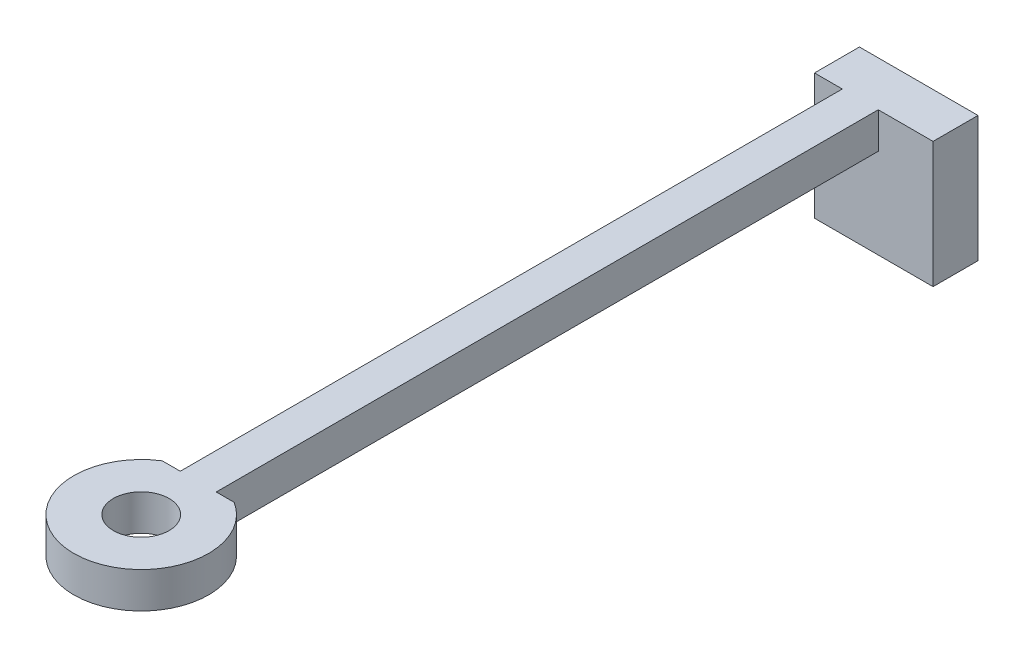
SolidWorks part; units mm, degrees
ref_plane "Спереди" through (0, 0, 0) normal (0, 0, 1) x (1, 0, 0)
ref_plane "Сверху" through (0, 0, 0) normal (0, 1, 0) x (1, 0, 0)
ref_plane "Справа" through (0, 0, 0) normal (1, 0, 0) x (0, 0, -1)
sketch "Sketch1" plane through (0, 0, 0) normal (0, 1, 0) x (1, 0, 0)
  line L0 (0, 45) -> (0, -45) construction
  line L1 (4, -45) -> (-4, -45)
  line L2 (4, -45) -> (4, 45)
  line L3 (4, 45) -> (-4, 45)
  line L4 (-4, -45) -> (-4, 45)
  line L5 (4, -45) -> (-4, 45) construction
  line L6 (4, 45) -> (-4, -45) construction
  circle A0 centre (0, -40) radius 3.1
  point P0 (0, 0)
  dimension "D3" = 6.2
  dimension "D1" = 8
  dimension "D2" = 90
  dimension "D4" = 5
extrude "Boss-Extrude1" add sketch "Sketch1" along normal blind 4
fillet "Fillet1" radius 4 2 edges at (-4, 2, 45) (4, 2, 45)
sketch "Sketch2" plane through (0, 4, 0) normal (0, 1, 0) x (1, 0, 0)
  circle A0 centre (0, -40) radius 7.5
  circle A1 centre (0, -40) radius 3.1
  circle A2 centre (0, -40) radius 3.1 construction
  dimension "D1" = 15
extrude "Boss-Extrude2" add sketch "Sketch2" against normal up to surface (4 mm away) up to face at (0, 0, 7.7314)
sketch "Sketch3" plane through (0, 4, 0) normal (0, 1, 0) x (1, 0, 0)
  line L0 (0, 45) -> (0, -39.2348) construction
  line L1 (4, 45) -> (-4, 45) construction
  line L2 (-4, -33.6557) -> (4, -33.6557) construction
  line L3 (2, -33.6557) -> (-2, -33.6557) construction
  line L4 (2, -33.6557) -> (2, 45)
  line L5 (2, 45) -> (-2, 45) construction
  line L6 (-2, -33.6557) -> (-2, 45)
  line L7 (2, -33.6557) -> (-2, 45) construction
  line L8 (2, 45) -> (-2, -33.6557) construction
  line L9 (-2, 45) -> (-4, 45)
  line L10 (-4, 45) -> (-4, -33.6557)
  line L11 (-4, -33.6557) -> (-2, -33.6557)
  line L12 (2, -33.6557) -> (4, -33.6557)
  line L13 (4, -33.6557) -> (4, 45)
  line L14 (4, 45) -> (2, 45)
  point P7 (0, 5.6721)
  dimension "D1" = 4
extrude "Cut-Extrude2" cut sketch "Sketch3" against normal through all
sketch "Sketch4" plane through (0, 0, 0) normal (0, -1, 0) x (1, 0, 0)
  line L0 (0, 40) -> (0, -45) construction
  line L1 (2, -45) -> (-2, -45) construction
  line L2 (0, -13.5) -> (0, -11.5) construction
  line L3 (0, -45) -> (-1, -45)
  line L4 (-1, -45) -> (-1, 33.6557)
  line L5 (-1, 33.6557) -> (0, 33.6557)
  line L6 (0, 33.6557) -> (0, -45)
  line L7 (-4, 33.6557) -> (-2, 33.6557) construction
  arc A0 (0, -11.5) -> (0, -13.5) centre (0, -12.5) ccw construction
  dimension "D2" = 1
  dimension "D1" = 52.5
  dimension "D3" = 1
revolve "Revolve1" add sketch "Sketch4" angle 360 about L0
sketch "Sketch5" plane through (0, 0, 0) normal (0, -1, 0) x (1, 0, 0)
  line L0 (1.5, -45) -> (1.5, 40) construction
  line L1 (2, -45) -> (1, -45) construction
  line L3 (-5.0954, -40) -> (8.0954, -40)
  line L4 (-5.0954, -40) -> (-5.0954, -45)
  line L5 (-5.0954, -45) -> (8.0954, -45)
  line L6 (8.0954, -40) -> (8.0954, -45)
  line L7 (-5.0954, -40) -> (8.0954, -45) construction
  line L8 (-5.0954, -45) -> (8.0954, -40) construction
  point P5 (1.5, -42.5)
  dimension "D1" = 5
extrude "Boss-Extrude5" add sketch "Sketch5" along normal blind 10 and the other way up to surface (4 mm away) other way up to face at (0, 4, 9.7445)
